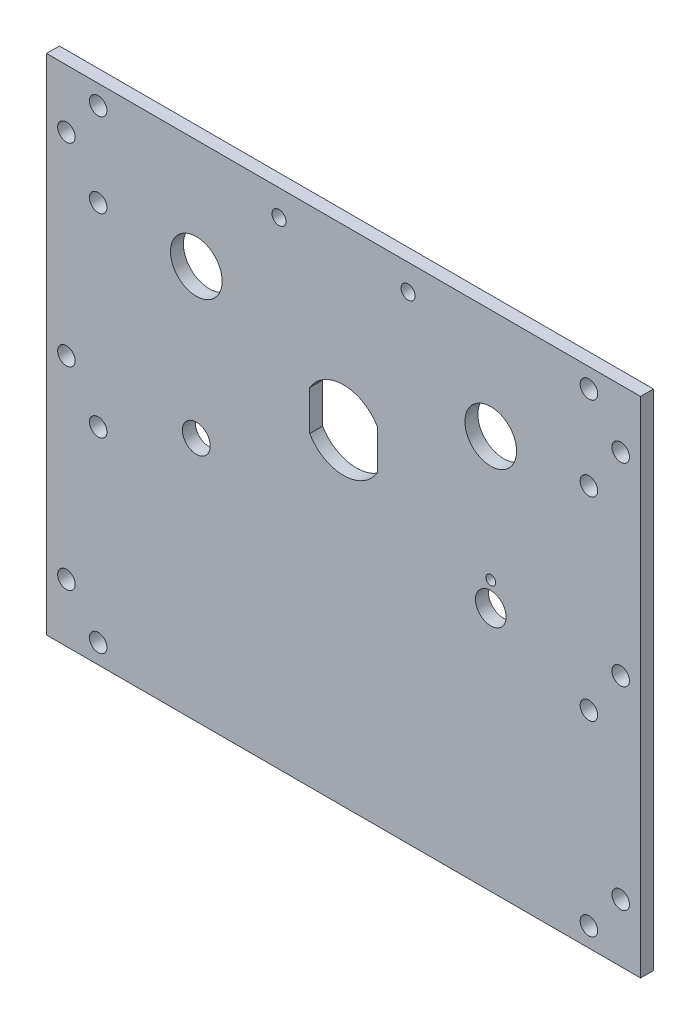
SolidWorks part; units mm, degrees
ref_plane "Front Plane" through (0, 0, 0) normal (0, 0, 1) x (1, 0, 0)
ref_plane "Top Plane" through (0, 0, 0) normal (0, 1, 0) x (1, 0, 0)
ref_plane "Right Plane" through (0, 0, 0) normal (1, 0, 0) x (0, 0, -1)
sketch "Sketch1" plane through (0, 0, 0) normal (0, 0, 1) x (1, 0, 0)
  line L8 (0, 123.825) -> (-146.05, 123.825)
  line L9 (-146.05, 123.825) -> (-146.05, 0)
  line L10 (-146.05, 0) -> (0, 0)
  line L11 (0, 0) -> (0, 123.825)
extrude "Boss-Extrude1" add sketch "Sketch1" against normal blind 3.175
hole_wizard "#6 Clearance Hole1" positions "Sketch3" profile "Sketch2" hole size "#6" standard "ANSI Inch" end condition through all
sketch "Sketch3" plane through (0, 0, -3.175) normal (0, 0, -1) x (-1, 0, 0)
  line L0 (88.9, 117.475) -> (57.15, 117.475) construction
  point P0 (12.7, 119.0625)
  point P9 (133.35, 119.0625)
  point P12 (141.1605, 109.5375)
  point P15 (133.35, 98.425)
  point P18 (141.1605, 61.9125)
  point P21 (133.35, 50.673)
  point P24 (133.35, 4.7625)
  point P27 (12.7, 4.7625)
  point P30 (12.7, 50.673)
  point P33 (12.7, 98.425)
  point P36 (4.8895, 109.5375)
  point P39 (141.1605, 14.2875)
  point P42 (4.8895, 14.2875)
  point P45 (4.8895, 61.9125)
sketch "Sketch2" plane through (-12.7, 119.0625, -3.175) normal (1, 0, 0) x (0, 1, 0)
  line L0 (0, 0) -> (0, 3.175)
  line L1 (0, 3.175) -> (2.1526, 3.175)
  line L2 (2.1526, 3.175) -> (2.1526, 0)
  line L5 (2.1526, 0) -> (0, 0)
  line L11 (0, -6.35) -> (0, 107.95) construction
  dimension "Thru Hole Dia." = 4.3053
  dimension "Thru Hole Depth" = 3.175
sketch "Sketch4" plane through (0, 0, -3.175) normal (0, 0, -1) x (-1, 0, 0)
  line L2 (81.3435, 85.0323) -> (81.3435, 75.2417)
  line L3 (64.7065, 75.2417) -> (64.7065, 85.0323)
  line L4 (40.58, 66.325) -> (33.08, 66.325) construction
  circle A0 centre (36.83, 96.901) radius 6.35
  circle A1 centre (36.83, 60.325) radius 3.7703
  circle A2 centre (109.22, 60.325) radius 3.429
  circle A3 centre (109.22, 96.901) radius 6.35
  circle A4 centre (36.83, 66.325) radius 1.1906
  arc A6 (81.3435, 85.0323) -> (64.7065, 85.0323) centre (73.025, 80.137) ccw
  arc A7 (64.7065, 75.2417) -> (81.3435, 75.2417) centre (73.025, 80.137) ccw
  dimension "D1" = 7.5406
  dimension "D2" = 12.7
  dimension "D3" = 6.858
  dimension "D4" = 2.3813
extrude "Cut-Extrude1" cut sketch "Sketch4" against normal through all
hole_wizard "#4 Clearance Hole1" positions "Sketch6" profile "Sketch5" hole size "#4" standard "ANSI Inch" end condition through all
sketch "Sketch6" plane through (0, 0, 0) normal (0, 0, 1) x (1, 0, 0)
  point P3 (-88.9, 117.475)
  point P6 (-57.15, 117.475)
sketch "Sketch5" plane through (-88.9, 117.475, 0) normal (1, 0, 0) x (0, -1, 0)
  line L0 (0, 0) -> (0, 3.175)
  line L1 (0, 3.175) -> (1.7272, 3.175)
  line L2 (1.7272, 3.175) -> (1.7272, 0)
  line L5 (1.7272, 0) -> (0, 0)
  line L11 (0, -6.35) -> (0, 107.95) construction
  dimension "Thru Hole Dia." = 3.4544
  dimension "Thru Hole Depth" = 3.175
